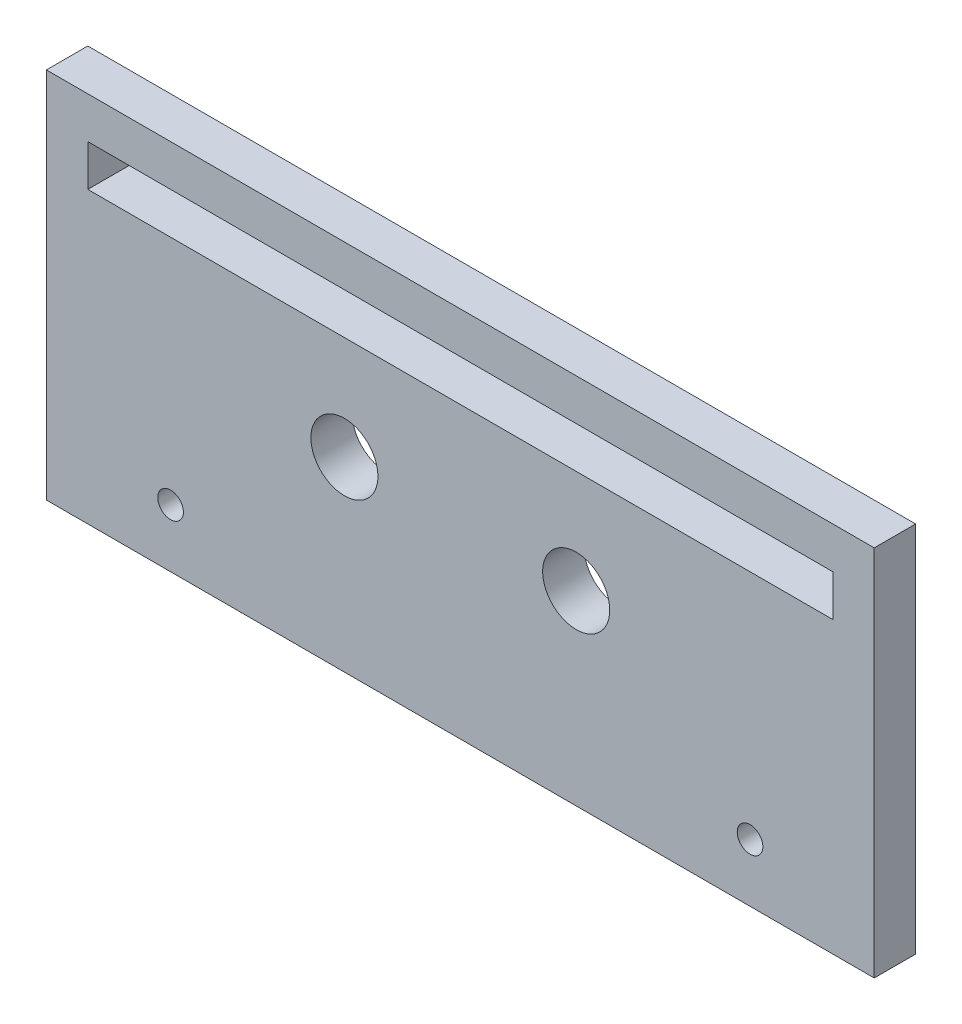
SolidWorks part; units mm, degrees
ref_plane "Plan de face" through (0, 0, 0) normal (0, 0, 1) x (1, 0, 0)
ref_plane "Plan de dessus" through (0, 0, 0) normal (0, 1, 0) x (1, 0, 0)
ref_plane "Plan de droite" through (0, 0, 0) normal (1, 0, 0) x (0, 0, -1)
sketch "Esquisse1" plane through (0, 0, 0) normal (0, 0, 1) x (1, 0, 0)
  line L0 (0, 0) -> (0, 16.8216) construction
  line L1 (-50, -22.5) -> (50, -22.5)
  line L2 (-50, -22.5) -> (-50, 22.5)
  line L3 (-50, 22.5) -> (50, 22.5)
  line L4 (50, -22.5) -> (50, 22.5)
  line L5 (-50, -22.5) -> (50, 22.5) construction
  line L6 (-50, 22.5) -> (50, -22.5) construction
  line L7 (0, 0) -> (42.1574, 0) construction
  line L13 (-45, 17.5) -> (45, 17.5)
  line L14 (-45, 17.5) -> (-45, 12.5)
  line L15 (-45, 12.5) -> (45, 12.5)
  line L16 (45, 17.5) -> (45, 12.5)
  circle A0 centre (-35, -15.5) radius 1.55
  circle A2 centre (35, -15.5) radius 1.55
  circle A7 centre (14, 0) radius 4.05
  circle A8 centre (-14, 0) radius 4.05
  point P0 (0, 0)
  dimension "D3" = 3.1
  dimension "D6" = 8.1
  dimension "D7" = 14
  dimension "D1" = 100
  dimension "D2" = 45
  dimension "D4" = 15
  dimension "D5" = 7
  dimension "D8" = 5
  dimension "D9" = 5
  dimension "D10" = 5
  dimension "D11" = 5
extrude "Boss.-Extru.1" add sketch "Esquisse1" against normal blind 5
